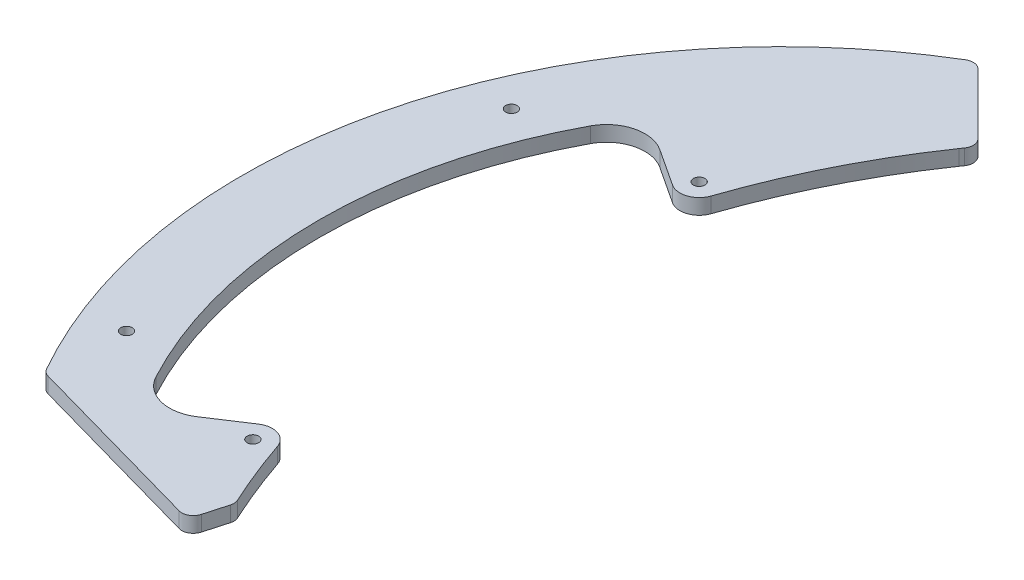
SolidWorks part; units mm, degrees
material "PMMA"
ref_plane "Front Plane" through (0, 0, 0) normal (0, 0, 1) x (1, 0, 0)
ref_plane "Top Plane" through (0, 0, 0) normal (0, 1, 0) x (1, 0, 0)
ref_plane "Right Plane" through (0, 0, 0) normal (1, 0, 0) x (0, 0, -1)
sketch "Sketch1" plane through (0, 0, 0) normal (0, 1, 0) x (1, 0, 0)
  circle A0 centre (0, 0) radius 140
  dimension "D1" = 280
extrude "Boss-Extrude1" add sketch "Sketch1" along normal blind 4
sketch "Sketch17" plane through (0, 0, 0) normal (0, -1, 0) x (1, 0, 0)
  line L0 (-50, 90) -> (-121.2436, 70)
  line L1 (-50, 90) -> (50, 90)
  line L2 (-121.2436, 70) -> (-121.2436, 140)
  line L3 (-121.2436, 140) -> (121.2436, 140)
  line L4 (121.2436, 140) -> (121.2436, 70)
  line L5 (121.2436, 70) -> (50, 90)
  circle A0 centre (0, 0) radius 140 construction
  dimension "D1" = 90
  dimension "D2" = 50
  dimension "D3" = 50
  dimension "D4" = 70
extrude "Cut-Extrude1" cut sketch "Sketch17" against normal up to next
sketch "Sketch19" plane through (0, 4, 0) normal (0, 1, 0) x (1, 0, 0)
  line L0 (-68.5894, 68.5894) -> (68.5894, -68.5894) construction
  line L1 (97, 40.1787) -> (40.1787, 97) construction
  line L2 (40.1787, 97) -> (-40.1787, 97) construction
  line L3 (-40.1787, 97) -> (-97, 40.1787) construction
  line L4 (-97, 40.1787) -> (-97, -40.1787) construction
  line L5 (-97, -40.1787) -> (-40.1787, -97) construction
  line L6 (-40.1787, -97) -> (40.1787, -97) construction
  line L7 (40.1787, -97) -> (97, -40.1787) construction
  line L8 (97, -40.1787) -> (97, 40.1787) construction
  line L9 (68.5894, 68.5894) -> (-68.5894, -68.5894) construction
  circle A0 centre (-79.196, -57.9828) radius 1.5
  circle A1 centre (-79.196, 57.9828) radius 1.5
  circle A2 centre (79.196, 57.9828) radius 1.5
  circle A3 centre (79.196, -57.9828) radius 1.5
  circle A4 centre (0, 0) radius 97 construction
  circle A5 centre (-57.9828, 79.196) radius 1.5
  circle A6 centre (57.9828, 79.196) radius 1.5
  circle A7 centre (57.9828, -79.196) radius 1.5
  circle A8 centre (-57.9828, -79.196) radius 1.5
  dimension "D5" = 3
  dimension "D1" = 15
  dimension "D6" = 97
extrude "Cut-Extrude3" cut sketch "Sketch19" against normal up to next
sketch "Sketch20" plane through (0, 4, 0) normal (0, 1, 0) x (1, 0, 0)
  line L0 (-70, 121.2436) -> (-50, 101.2436)
  line L1 (-50, 101.2436) -> (50, 101.2436)
  line L2 (50, 101.2436) -> (70, 121.2436)
  arc A1 (121.2436, -70) -> (-121.2436, -70) centre (0, 0) ccw construction
  dimension "D1" = 140
  dimension "D2" = 100
  dimension "D3" = 50
extrude "Cut-Extrude4" cut sketch "Sketch20" against normal up to next
sketch "Sketch21" plane through (0, 4, 0) normal (0, 1, 0) x (1, 0, 0)
  line L0 (-52.1633, 87.3282) -> (0, 50)
  line L1 (0, 50) -> (52.1633, 87.3282)
  line L2 (66.2648, 73.5916) -> (30, 20)
  line L3 (30, 20) -> (67.2983, -75.56)
  line L4 (49.6537, -84.7301) -> (0, -10) construction
  line L5 (0, -10) -> (-49.6537, -84.7301) construction
  line L6 (-67.2983, -75.56) -> (-30, 20)
  line L7 (-30, 20) -> (-66.2648, 73.5916)
  line L8 (-67.2983, -75.56) -> (-72.9344, -90)
  line L9 (-72.9344, -90) -> (72.9344, -90)
  line L10 (72.9344, -90) -> (67.2983, -75.56)
  line L11 (-50, -90) -> (50, -90) construction
  line L12 (-68.5894, 68.5894) -> (68.5894, -68.5894) construction
  line L13 (97, 40.1787) -> (40.1787, 97) construction
  line L14 (40.1787, 97) -> (-40.1787, 97) construction
  line L15 (-40.1787, 97) -> (-97, 40.1787) construction
  line L16 (-97, 40.1787) -> (-97, -40.1787) construction
  line L17 (-97, -40.1787) -> (-40.1787, -97) construction
  line L18 (-40.1787, -97) -> (40.1787, -97) construction
  line L19 (40.1787, -97) -> (97, -40.1787) construction
  line L20 (97, -40.1787) -> (97, 40.1787) construction
  line L21 (68.5894, 68.5894) -> (-68.5894, -68.5894) construction
  arc A0 (-66.2648, 73.5916) -> (-52.1633, 87.3282) centre (-57.9828, 79.196) cw
  arc A1 (66.2648, 73.5916) -> (52.1633, 87.3282) centre (57.9828, 79.196) ccw
  arc A2 (-49.6537, -84.7301) -> (-67.2983, -75.56) centre (-57.9828, -79.196) cw construction
  arc A3 (67.2983, -75.56) -> (49.6537, -84.7301) centre (57.9828, -79.196) cw construction
  circle A5 centre (0, 0) radius 97 construction
  dimension "D2" = 10
  dimension "D3" = 15
  dimension "D8" = 97
extrude "Cut-Extrude5" [suppressed] cut sketch "Sketch21" against normal up to next
fillet "Fillet1" [suppressed] radius 20
fillet "Fillet2" radius 10 2 edges at (50, 2, -101.2436) (-50, 2, -101.2436)
sketch "Sketch22" plane through (0, 4, 0) normal (0, 1, 0) x (1, 0, 0)
  line L1 (85, 24) -> (118, 24)
  line L2 (85, 24) -> (85, -24)
  line L3 (85, -24) -> (118, -24)
  line L4 (118, 24) -> (118, -24)
  line L5 (-118, 26) -> (-85, 26)
  line L6 (-118, 26) -> (-118, -27)
  line L7 (-118, -27) -> (-85, -27)
  line L8 (-85, 26) -> (-85, -27)
  dimension "D1" = 85
  dimension "D2" = 85
  dimension "D3" = 48
  dimension "D4" = 53
  dimension "D5" = 33
  dimension "D6" = 33
  dimension "D7" = 26
  dimension "D8" = 24
extrude "Cut-Extrude6" [suppressed] cut sketch "Sketch22" against normal up to next
fillet "Fillet3" [suppressed] radius 3
sketch "Sketch23" plane through (0, 4, 0) normal (0, 1, 0) x (1, 0, 0)
  line L0 (-67.0725, -74.5764) -> (-73.1897, -96.3671)
  line L1 (-52.9289, 104.1725) -> (-50.8743, 102.1178)
  line L2 (-121.2436, -70) -> (-50, -90) construction
  line L3 (-70, 121.2436) -> (-52.9289, 104.1725) construction
  arc A0 (-52.9289, 99.196) -> (-67.0725, -74.5764) centre (91.2417, 0) ccw
  circle A1 centre (-57.9828, 79.196) radius 1.5 construction
  arc A3 (-67.0725, -74.5764) -> (-52.9289, -99.196) centre (91.2417, 0) ccw construction
  circle A4 centre (-57.9828, -79.196) radius 1.5 construction
  arc A5 (-52.9289, 99.196) -> (-50.8743, 102.1178) centre (91.2417, 0) cw
  dimension "D1" = 20
  dimension "D2" = 20
  dimension "D3" = 175
  dimension "D4" = 90
  dimension "D5" = 10
extrude "Cut-Extrude8" cut sketch "Sketch23" against normal through all and the other way through all
sketch "Sketch24" plane through (0, 4, 0) normal (0, 1, 0) x (1, 0, 0)
  line L0 (0, 0) -> (-100.309, 65.8643)
  line L1 (-100.309, -65.8643) -> (0, 0)
  arc A0 (-100.309, 65.8643) -> (-100.309, -65.8643) centre (0, 0) ccw
  circle A1 centre (-79.196, 57.9828) radius 1.5 construction
  circle A2 centre (-79.196, -57.9828) radius 1.5 construction
  arc A3 (-70, 121.2436) -> (-121.2436, -70) centre (0, 0) ccw construction
  dimension "D2" = 5
  dimension "D3" = 20
  dimension "D1" = 5
extrude "Cut-Extrude9" cut sketch "Sketch24" against normal up to next
fillet "Fillet4" radius 5 2 edges at (-76.4117, 2, 50.1731) (-76.4117, 2, -50.1731)
fillet "Fillet6" radius 10 2 edges at (-100.309, 2, -65.8643) (-100.309, 2, 65.8643)
sketch "Sketch25" plane through (0, 4, 0) normal (0, 1, 0) x (1, 0, 0)
  circle A0 centre (-120, 50) radius 1.5
  circle A1 centre (-120, -50) radius 1.5
  dimension "D1" = 3
  dimension "D2" = 50
  dimension "D3" = 50
  dimension "D4" = 120
extrude "Cut-Extrude10" cut sketch "Sketch25" against normal up to next
fillet "Fillet5" radius 3 5 edges at (-70, 2, -121.2436) (-50.8743, 2, -102.1178) (-67.0725, 2, 74.5764) (-69.8389, 2, 84.4307) (-121.2436, 2, 70)
equation "\"D3@Sketch20\" = \"D2@Sketch20\" / 2"
